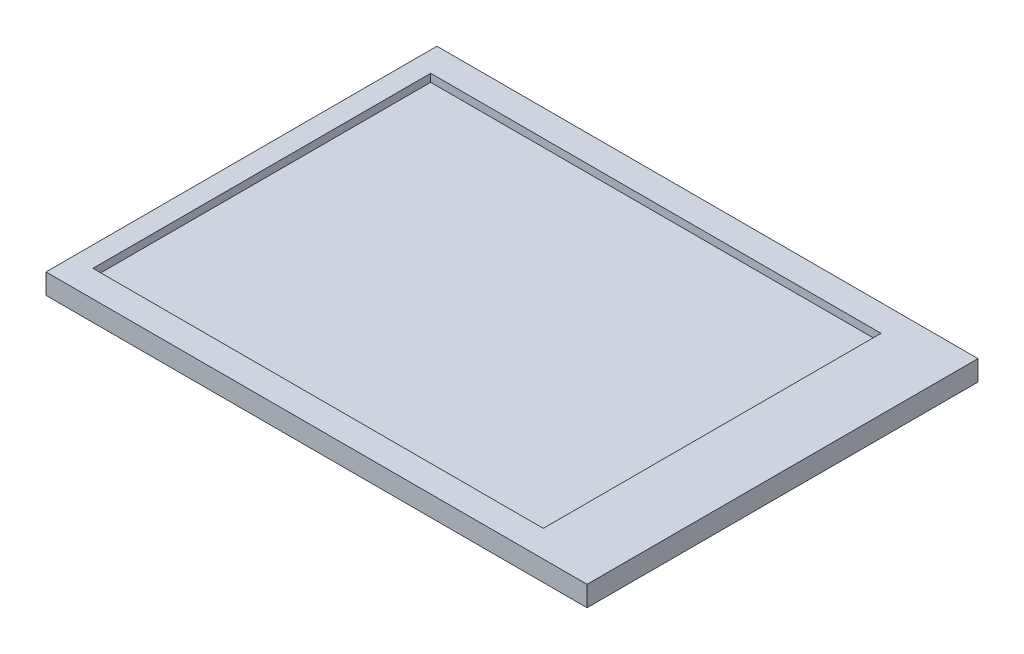
SolidWorks part; units mm, degrees
ref_plane "前视基准面" through (0, 0, 0) normal (0, 0, 1) x (1, 0, 0)
ref_plane "上视基准面" through (0, 0, 0) normal (0, 1, 0) x (1, 0, 0)
ref_plane "右视基准面" through (0, 0, 0) normal (1, 0, 0) x (0, 0, -1)
other "Configuration Table"
sketch "LCD外壳" plane through (0, 0, 0) normal (0, 1, 0) x (1, 0, 0)
  line L1 (-34.6, -25) -> (34.6, -25)
  line L2 (-34.6, -25) -> (-34.6, 25)
  line L3 (-34.6, 25) -> (34.6, 25)
  line L4 (34.6, -25) -> (34.6, 25)
  line L5 (-34.6, -25) -> (34.6, 25) construction
  line L6 (-34.6, 25) -> (34.6, -25) construction
  line L7 (-32, -21.6) -> (25.6, -21.6)
  line L8 (-32, -21.6) -> (-32, 21.6)
  line L9 (-32, 21.6) -> (25.6, 21.6)
  line L10 (25.6, -21.6) -> (25.6, 21.6)
  line L11 (-32, -21.6) -> (25.6, 21.6) construction
  line L12 (-32, 21.6) -> (25.6, -21.6) construction
  point P0 (0, 0)
  point P6 (-3.2, 0)
  dimension "D1" = 50
  dimension "D2" = 69.2
  dimension "D3" = 43.2
  dimension "D4" = 57.6
  dimension "D5" = 2.6
  dimension "D6" = 3.4
extrude "凸台-拉伸2" add sketch "LCD外壳" against normal blind 2.6 contours L1 L4 L3 L2 L10 L7 L8 L9 | L7 L10 L9 L8 region at (-33.7463, 0, 0) region at (-3.2, 0, 0)
extrude "切除-拉伸1" cut sketch "LCD外壳<3>" against normal blind 1 contours L7 L10 L9 L8 region at (-3.2, 0, 0)
sketch "LCD外壳<3>" plane through (0, 0, 0) normal (0, 1, 0) x (1, 0, 0) same geometry as "LCD外壳"
